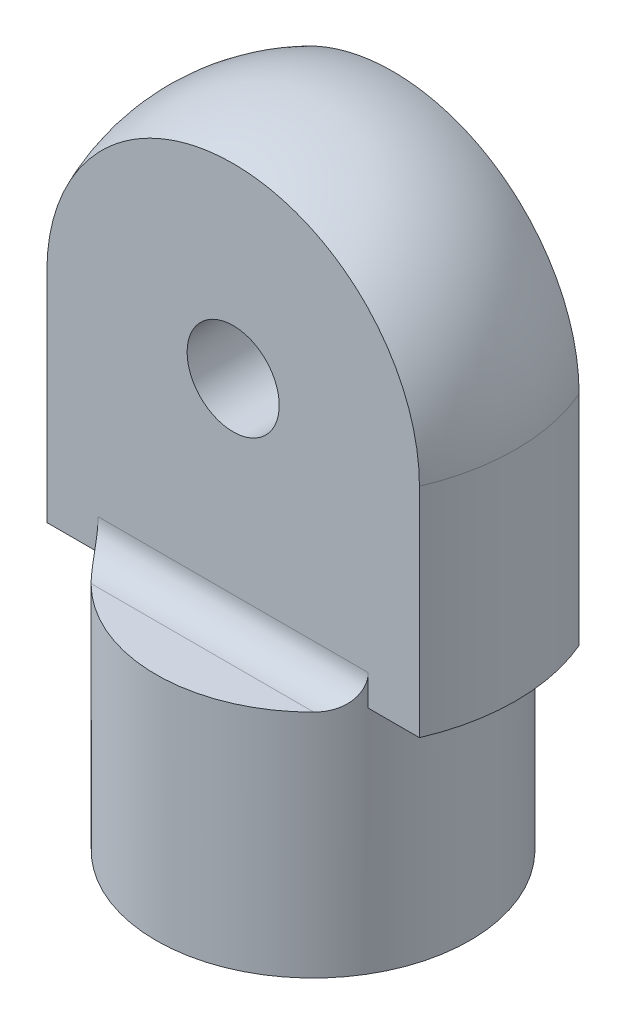
SolidWorks part; units mm, degrees
ref_plane "Front Plane" through (0, 0, 0) normal (0, 0, 1) x (1, 0, 0)
ref_plane "Top Plane" through (0, 0, 0) normal (0, 1, 0) x (1, 0, 0)
ref_plane "Right Plane" through (0, 0, 0) normal (1, 0, 0) x (0, 0, -1)
sketch "Sketch1" plane through (0, 0, 0) normal (0, 1, 0) x (1, 0, 0)
  circle A0 centre (0, 0) radius 12.9794
  dimension "D1" = 25.9588
extrude "Boss-Extrude1" add sketch "Sketch1" along normal blind 19.05
sketch "Sketch2" plane through (0, 0, 0) normal (1, 0, 0) x (0, 0, -1)
  line L0 (0, 10.4775) -> (0, -10.4775) construction
  line L3 (12.9794, 19.05) -> (-12.9794, 19.05) construction
  line L4 (0, 19.05) -> (0, 53.8256)
  line L5 (-16.764, 37.0616) -> (-16.764, 19.05)
  line L6 (-16.764, 19.05) -> (0, 19.05)
  arc A0 (0, 53.8256) -> (-16.764, 37.0616) centre (0, 37.0616) ccw
  dimension "D3" = 33.528
revolve "Revolve1" add sketch "Sketch2" angle 360 about L4
sketch "Sketch3" plane through (0, 0, 0) normal (1, 0, 0) x (0, 0, -1)
  line L1 (-6.604, 19.05) -> (-28.2389, 19.05)
  line L2 (-6.604, 19.05) -> (-6.604, 59.8399)
  line L3 (-6.604, 59.8399) -> (-28.2389, 59.8399)
  line L4 (-28.2389, 19.05) -> (-28.2389, 59.8399)
  line L5 (0, 18.4404) -> (0, -18.4404) construction
  line L6 (6.604, 19.05) -> (31.5571, 19.05)
  line L7 (6.604, 19.05) -> (6.604, 63.5882)
  line L8 (6.604, 63.5882) -> (31.5571, 63.5882)
  line L9 (31.5571, 19.05) -> (31.5571, 63.5882)
  line L10 (-12.9794, 19.05) -> (12.9794, 19.05) construction
  point P4 (-6.604, 22.7982)
  dimension "D1" = 13.208
  dimension "D2" = 6.604
extrude "Cut-Extrude1" cut sketch "Sketch3" against normal through all both and the other way through all
sketch "Sketch4" plane through (0, 0, -6.604) normal (0, 0, -1) x (-1, 0, 0)
  circle A0 centre (0, 37.0616) radius 3.81
  arc A1 (15.4084, 37.0616) -> (-15.4084, 37.0616) centre (0, 37.0616) ccw construction
extrude "Cut-Extrude2" cut sketch "Sketch4" against normal through all both
sketch "Sketch6" plane through (0, 0, 6.604) normal (0, 0, 1) x (1, 0, 0)
  point P0 (0, 37.0616)
fillet "Fillet1" radius 2.54 2 edges at (0, 19.05, -6.604) (0, 19.05, 6.604)
